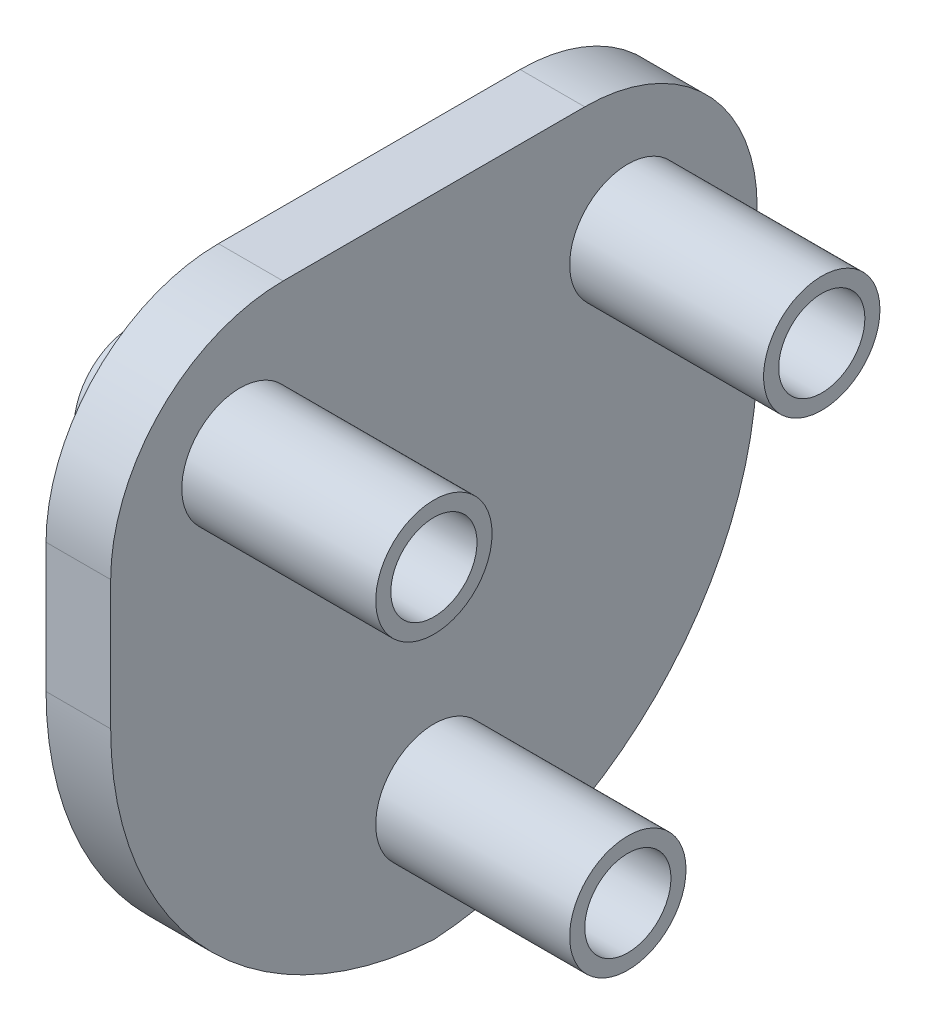
SolidWorks part; units mm, degrees
ref_plane "Front Plane" through (0, 0, 0) normal (0, 0, 1) x (1, 0, 0)
ref_plane "Top Plane" through (0, 0, 0) normal (0, 1, 0) x (1, 0, 0)
ref_plane "Right Plane" through (0, 0, 0) normal (1, 0, 0) x (0, 0, -1)
sketch "Sketch1" plane through (0, 0, 0) normal (0, 0, 1) x (1, 0, 0)
  line L13 (7.5, -75) -> (-7.5, -75)
  line L14 (7.5, -75) -> (7.5, 75)
  line L15 (7.5, 75) -> (-7.5, 75)
  line L16 (-7.5, -75) -> (-7.5, 75)
  line L17 (7.5, -75) -> (-7.5, 75) construction
  line L18 (7.5, 75) -> (-7.5, -75) construction
  point P0 (0, 0)
  dimension "D1" = 150
  dimension "D2" = 15
extrude "Boss-Extrude1" add sketch "Sketch1" along normal blind 75 and the other way blind 75
sketch "Sketch2" plane through (7.5, 0, 0) normal (1, 0, 0) x (0, 0, -1)
  line L0 (-75, 75) -> (75, -75) construction
  line L1 (-75, -75) -> (75, 75) construction
  line L2 (0, 44.2539) -> (0, -44.2539) construction
  circle A1 centre (0, -45) radius 13.5
  circle A2 centre (-45, 45) radius 13.5
  circle A3 centre (45, 45) radius 13.5
  point P10 (0, 0)
  point P17 (0, 0)
  point P18 (0, 0)
  dimension "D1" = 27
  dimension "D2" = 27
  dimension "D4" = 27
  dimension "D3" = 90
  dimension "D5" = 45
extrude "Boss-Extrude2" add sketch "Sketch2" along normal blind 45 and the other way blind 25
hole_wizard "Ø20.0mm Dowel Hole1" positions "Sketch5" profile "Sketch4" hole size "Ø20.0" standard "ANSI Metric" end condition through all
sketch "Sketch5" plane through (52.5, 0, 0) normal (1, 0, 0) x (0, 0, -1)
  point P0 (-45, 45)
  point P3 (45, 45)
  point P6 (0, -45)
sketch "Sketch4" plane through (52.5, 45, 45) normal (0, 1, 0) x (0, 0, -1)
  line L0 (0, 0) -> (0, 70)
  line L1 (0, 70) -> (10, 70)
  line L2 (10, 70) -> (10, 0)
  line L5 (10, 0) -> (0, 0)
  line L11 (0, -6.35) -> (0, 107.95) construction
  dimension "Thru Hole Dia." = 20
  dimension "Thru Hole Depth" = 70
fillet "Fillet2" radius 80 2 edges at (0, -75, -75) (0, -75, 75)
fillet "Fillet3" radius 40 2 edges at (0, 75, -75) (0, 75, 75)
